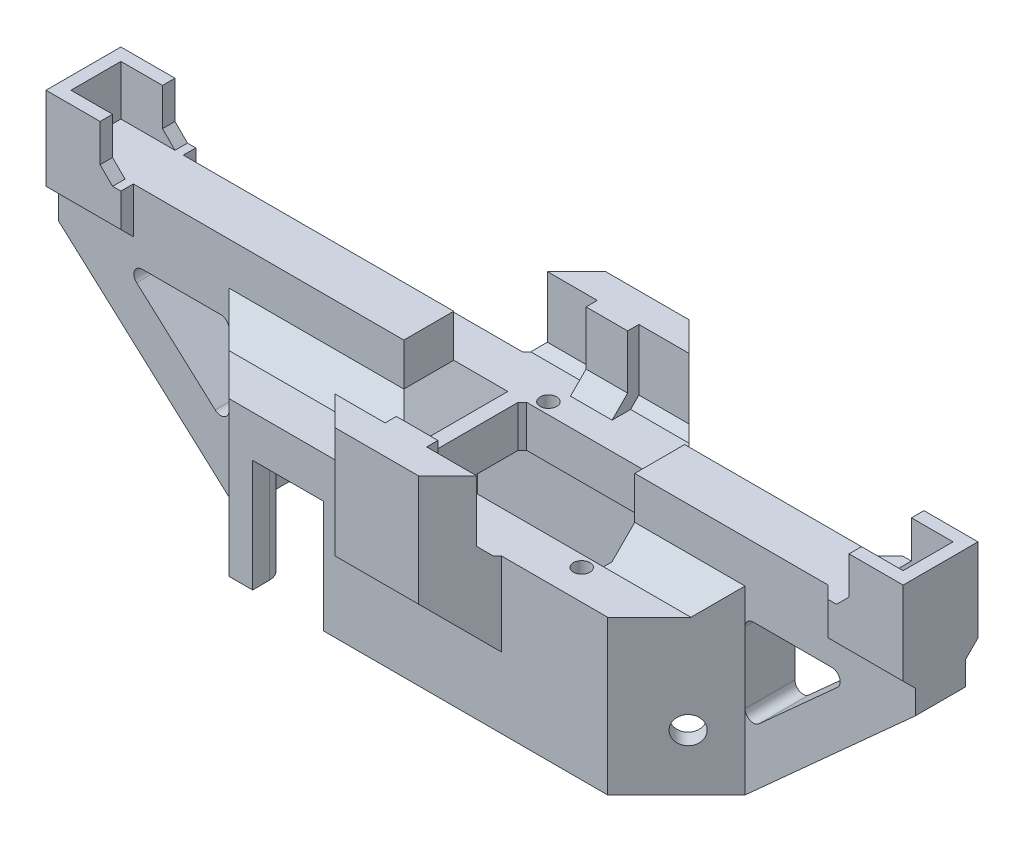
SolidWorks part; units mm, degrees
note: The reader was unsure of these and kept them because the rebuilt part matched: shared geometry of "Sketch17<3>".
ref_plane "Front Plane" through (0, 0, 0) normal (0, 0, 1) x (1, 0, 0)
ref_plane "Top Plane" through (0, 0, 0) normal (0, 1, 0) x (1, 0, 0)
ref_plane "Right Plane" through (0, 0, 0) normal (1, 0, 0) x (0, 0, -1)
sketch "Sketch1" plane through (0, 0, 0) normal (0, 1, 0) x (1, 0, 0)
  line L7 (-100, -6) -> (100, -6)
  line L8 (-100, -6) -> (-100, 6)
  line L9 (-100, 6) -> (100, 6)
  line L10 (100, -6) -> (100, 6)
  line L11 (-100, -6) -> (100, 6) construction
  line L12 (-100, 6) -> (100, -6) construction
  point P0 (0, 0)
  point P7 (0, 0)
  dimension "D2" = 200
  dimension "D3" = 12
extrude "Boss-Extrude2" add sketch "Sketch1" along normal blind 10
sketch "Sketch4" plane through (0, 0, 0) normal (0, 1, 0) x (1, 0, 0)
  line L1 (-10, -32.5) -> (10, -32.5)
  line L2 (-10, -32.5) -> (-10, 32.5)
  line L3 (-10, 32.5) -> (10, 32.5)
  line L4 (10, -32.5) -> (10, 32.5)
  line L5 (-10, -32.5) -> (10, 32.5) construction
  line L6 (-10, 32.5) -> (10, -32.5) construction
  point P0 (0, 0)
  dimension "D1" = 65
  dimension "D2" = 20
extrude "Boss-Extrude3" add sketch "Sketch4" along normal up to surface (10 mm away) up to face at (0, 10, 0)
sketch "Sketch5" plane through (0, 0, 0) normal (0, 1, 0) x (1, 0, 0)
  line L1 (-45.5, -22.5) -> (45.5, -22.5)
  line L2 (-45.5, -22.5) -> (-45.5, 22.5)
  line L3 (-45.5, 22.5) -> (45.5, 22.5)
  line L4 (45.5, -22.5) -> (45.5, 22.5)
  line L5 (-45.5, -22.5) -> (45.5, 22.5) construction
  line L6 (-45.5, 22.5) -> (45.5, -22.5) construction
  point P0 (0, 0)
  dimension "D1" = 91
  dimension "D2" = 45
extrude "Boss-Extrude4" add sketch "Sketch5" along normal up to surface (10 mm away) up to face at (0, 10, 0)
sketch "Sketch6" plane through (0, 10, 0) normal (0, 1, 0) x (1, 0, 0)
  line L1 (-10, -12.5) -> (35.5, -12.5)
  line L2 (-10, -12.5) -> (-10, 12.5)
  line L3 (-10, 12.5) -> (35.5, 12.5)
  line L4 (35.5, -12.5) -> (35.5, 12.5)
  line L5 (-10, -12.5) -> (35.5, 12.5) construction
  line L6 (-10, 12.5) -> (35.5, -12.5) construction
  point P0 (12.75, 0)
  dimension "D1" = 25
  dimension "D2" = 45.5
  dimension "D3" = 10
extrude "Cut-Extrude2" cut sketch "Sketch6" against normal through all
sketch "Sketch7" plane through (0, 10, 0) normal (0, 1, 0) x (1, 0, 0)
  line L0 (35.5, -12.5) -> (35.5, 12.5) construction
  line L1 (-100, 6) -> (-20, 6)
  line L2 (-100, 6) -> (-100, -6)
  line L3 (-100, -6) -> (-20, -6)
  line L4 (-20, 6) -> (-20, -6)
  line L5 (100, 6) -> (35.5, 6)
  line L6 (100, 6) -> (100, -6)
  line L7 (100, -6) -> (35.5, -6)
  line L8 (35.5, 6) -> (35.5, -6)
  line L9 (45.5, -6) -> (100, -6) construction
  line L10 (-100, -6) -> (-45.5, -6) construction
  dimension "D1" = 20
extrude "Boss-Extrude5" add sketch "Sketch7" along normal blind 16.7
sketch "Sketch8" plane through (0, 10, 0) normal (0, 1, 0) x (1, 0, 0)
  line L0 (10, 22.5) -> (10, 32.5) construction
  line L1 (-10, 32.5) -> (10, 32.5)
  line L2 (-10, 32.5) -> (-10, 25.5)
  line L3 (-10, 25.5) -> (10, 25.5)
  line L4 (10, 32.5) -> (10, 25.5)
  line L6 (-5, 22.8) -> (5, 22.8)
  line L7 (-5, 22.8) -> (-5, 25.5)
  line L8 (-5, 25.5) -> (5, 25.5)
  line L9 (5, 22.8) -> (5, 25.5)
  line L10 (-5, 22.8) -> (5, 25.5) construction
  line L11 (-5, 25.5) -> (5, 22.8) construction
  point P7 (0, 24.15)
  line M6 (10, 22.5) -> (10, 32.5)
  line M7 (10, 32.5) -> (-10, 32.5)
  line M8 (-10, 32.5) -> (-10, 22.5)
  dimension "D1" = 22.8
  dimension "D2" = 7
  dimension "D3" = 10
extrude "Boss-Extrude6" add sketch "Sketch8" along normal up to surface (16.7 mm away) contours L3 M8 M6 M7 | L6 L9 L3 L7 up to face at (67.75, 26.7, 0)
mirror "Mirror1" about plane through (0, 0, 0) normal (0, 0, 1) of "Boss-Extrude6"
chamfer "Chamfer1" distance 10 angle 45 4 edges at (-10, 5, 22.5) (10, 5, 22.5) (-10, 5, -22.5) (10, 5, -22.5)
chamfer "Chamfer3" distance 2 angle 45 4 edges at (11, 10, 25.5) (-11, 10, 25.5) (11, 10, -25.5) (-11, 10, -25.5)
chamfer "Chamfer4" distance 16.5 angle 45 4 edges at (45.5, 5, -6) (-45.5, 5, -6) (-45.5, 5, 6) (45.5, 5, 6)
chamfer "Chamfer5" distance 6.5 angle 45 1 edges at (-20, 10, 0)
chamfer "Chamfer6" distance 6.5 angle 45 4 edges at (-37.75, 10, -6) (48.75, 10, -6) (48.75, 10, 6) (-37.75, 10, 6)
chamfer "Chamfer7" distance 3.75 angle 45 2 edges at (0, 10, 22.8) (0, 10, -22.8)
sketch "Sketch9" plane through (0, 0, 6) normal (0, 0, 1) x (1, 0, 0)
  line L0 (-100, 26.7) -> (-100, 0) construction
  line L1 (-100, 18.7) -> (-85, 18.7)
  line L2 (-100, 18.7) -> (-100, 26.7)
  line L3 (-100, 26.7) -> (-85, 26.7)
  line L4 (-85, 18.7) -> (-85, 26.7)
  line L5 (-100, 26.7) -> (-20, 26.7) construction
  line L7 (-90, 26.7) -> (-100, 26.7)
  line L8 (-90, 26.7) -> (-90, 38.7)
  line L9 (-90, 38.7) -> (-100, 38.7)
  line L10 (-100, 26.7) -> (-100, 38.7)
  line M5 (-100, 26.7) -> (-100, 0)
  line M11 (-20, 26.7) -> (-100, 26.7)
  dimension "D1" = 10
  dimension "D2" = 8
  dimension "D3" = 12
  dimension "D4" = 15
extrude "Boss-Extrude7" add sketch "Sketch9" along normal blind 3 contours L10 L3 L8 L9 | L1 L4 L3 M11 M5
mirror "Mirror3" about plane through (0, 0, 0) normal (1, 0, 0) of "Boss-Extrude7" second plane through (0, 0, 0) second plane normal (0, 0, 1)
sketch "Sketch10" plane through (-100, 0, 0) normal (-1, 0, 0) x (0, 0, 1)
  line L0 (-6, 38.7) -> (6, 38.7)
  line L12 (6, 26.7) -> (-6, 26.7)
  line L13 (-6, 26.7) -> (-6, 38.7)
  line L14 (-6, 38.7) -> (-9, 38.7)
  line L15 (-9, 38.7) -> (-9, 18.7)
  line L16 (-9, 18.7) -> (-6, 18.7)
  line L17 (-6, 18.7) -> (-6, 0)
  line L18 (-6, 0) -> (6, 0)
  line L19 (6, 0) -> (6, 18.7)
  line L20 (6, 18.7) -> (9, 18.7)
  line L21 (9, 18.7) -> (9, 38.7)
  line L22 (9, 38.7) -> (6, 38.7)
  line L23 (6, 38.7) -> (6, 26.7)
  line L26 (-6, 38.7) -> (-9, 38.7)
  line L27 (-9, 38.7) -> (-9, 18.7)
  line L28 (-9, 18.7) -> (-6, 18.7)
  line L29 (-6, 18.7) -> (-6, 0)
  line L31 (6, 0) -> (6, 18.7)
  line L32 (6, 18.7) -> (9, 18.7)
  line L33 (9, 18.7) -> (9, 38.7)
  line L34 (9, 38.7) -> (6, 38.7)
  line L41 (-6, 0) -> (6, 0)
  dimension "D1" = 0
extrude "Boss-Extrude8" add sketch "Sketch10" along normal blind 3
mirror "Mirror4" about plane through (0, 0, 0) normal (1, 0, 0) of "Boss-Extrude8"
chamfer "Chamfer10" distance 3 angle 45 4 edges at (-90, 26.7, 7.5) (-90, 26.7, -7.5) (90, 26.7, 7.5) (90, 26.7, -7.5)
chamfer "Chamfer11" distance 3 angle 45 16 edges at (-94, 18.7, 6) (-85, 18.7, 7.5) (-94, 18.7, -6) (-85, 18.7, -7.5) (85, 26.7, 7.5) (85, 18.7, 7.5) (94, 18.7, 6) (85, 22.7, 6) (94, 18.7, -6) (85, 22.7, -6) (85, 18.7, -7.5) (85, 26.7, -7.5) (-103, 18.7, -7.5) (-103, 18.7, 7.5) (103, 18.7, 7.5) (103, 18.7, -7.5)
chamfer "Chamfer12" distance 1 angle 45 4 edges at (-10, 5, 12.5) (35.5, 5, 12.5) (35.5, 5, -12.5) (-10, 5, -12.5)
sketch "Sketch11" plane through (0, 0, 0) normal (0, -1, 0) x (1, 0, 0)
  line L0 (-20, 22.5) -> (20, 22.5)
  line L1 (-20, -22.5) -> (20, -22.5)
  line L2 (62, 6) -> (62, -6)
  line L3 (-62, 6) -> (-62, -6)
  line L4 (-58, 4.3431) -> (-58, -4.3431)
  line L5 (-58, -4.3431) -> (-43.8431, -18.5)
  line L6 (-43.8431, -18.5) -> (-20, -18.5)
  line L7 (-20, -18.5) -> (20, -18.5)
  line L8 (20, -18.5) -> (43.8431, -18.5)
  line L9 (43.8431, -18.5) -> (58, -4.3431)
  line L10 (58, 4.3431) -> (58, -4.3431)
  line L11 (58, 4.3431) -> (43.8431, 18.5)
  line L12 (43.8431, 18.5) -> (20, 18.5)
  line L13 (-20, 18.5) -> (20, 18.5)
  line L14 (-20, 18.5) -> (-43.8431, 18.5)
  line L15 (-43.8431, 18.5) -> (-58, 4.3431)
  line L20 (62, -6) -> (103, -6)
  line L21 (103, -6) -> (103, 6)
  line L22 (103, 6) -> (62, 6)
  line L23 (62, 6) -> (45.5, 22.5)
  line L24 (45.5, 22.5) -> (20, 22.5)
  line L25 (20, 22.5) -> (10, 32.5)
  line L26 (10, 32.5) -> (-10, 32.5)
  line L27 (-10, 32.5) -> (-20, 22.5)
  line L28 (-20, 22.5) -> (-45.5, 22.5)
  line L29 (-45.5, 22.5) -> (-62, 6)
  line L30 (-62, 6) -> (-103, 6)
  line L32 (-103, -6) -> (-62, -6)
  line L33 (-62, -6) -> (-45.5, -22.5)
  line L34 (-45.5, -22.5) -> (-20, -22.5)
  line L35 (-20, -22.5) -> (-10, -32.5)
  line L36 (-10, -32.5) -> (10, -32.5)
  line L37 (10, -32.5) -> (20, -22.5)
  line L38 (20, -22.5) -> (45.5, -22.5)
  line L39 (45.5, -22.5) -> (62, -6)
  line L43 (62, 6) -> (45.5, 22.5)
  line L44 (45.5, 22.5) -> (20, 22.5)
  line L48 (-20, 22.5) -> (-45.5, 22.5)
  line L49 (-45.5, 22.5) -> (-62, 6)
  line L53 (-62, -6) -> (-45.5, -22.5)
  line L54 (-45.5, -22.5) -> (-20, -22.5)
  line L58 (20, -22.5) -> (45.5, -22.5)
  line L59 (45.5, -22.5) -> (62, -6)
  line L76 (-103, 6) -> (-103, -6)
  dimension "D1" = 0
  dimension "D2" = 4
extrude "Boss-Extrude9" add sketch "Sketch11" along normal blind 27
chamfer "Chamfer13" distance 10 angle 45 2 edges at (0, 0, -22.5) (0, 0, 22.5)
sketch "Sketch14" plane through (0, 0, 0) normal (0, -1, 0) x (1, 0, 0)
  line L4 (62, 6) -> (62, -6)
  line L5 (62, -6) -> (103, -6)
  line L6 (103, -6) -> (103, 6)
  line L7 (103, 6) -> (62, 6)
  line L8 (62, 6) -> (62, -6)
  line L9 (62, -6) -> (103, -6)
  line L10 (103, -6) -> (103, 6)
  line L11 (103, 6) -> (62, 6)
  dimension "D1" = 0
extrude "Cut-Extrude4" cut sketch "Sketch14" against normal up to surface (10 mm away) up to face at (0.125, 10, 0)
sketch "Sketch16" plane through (0, 0, -6) normal (0, 0, -1) x (-1, 0, 0)
  line L0 (-103, 10) -> (-62, -27)
  line L1 (-62, -27) -> (-62, -13.53)
  line L2 (-62, -27) -> (-62, 10) construction
  line L3 (-62, -13.53) -> (-88.0738, 10)
  line L4 (-103, 10) -> (-62, 10) construction
  line L5 (-88.0738, 10) -> (-103, 10)
  dimension "D1" = 10
extrude "Boss-Extrude11" add sketch "Sketch16" against normal up to surface (12 mm away) up to face at (70.625, 17.225, 6)
mirror "Mirror6" about plane through (0, 0, 0) normal (1, 0, 0) of "Cut-Extrude4", "Boss-Extrude11"
fillet "Fillet2" radius 2 6 edges at (-62, -13.53, 0) (-62, 10, 0) (-88.0738, 10, 0) (62, -13.53, 0) (88.0738, 10, 0) (62, 10, 0)
sketch "Sketch17" plane through (0, 0, 0) normal (0, -1, 0) x (1, 0, 0)
  circle A0 centre (-43.8431, 18.5) radius 2
  circle A1 centre (-43.8431, 18.5) radius 4
  line M9 (43.8431, 18.5) -> (-43.8431, 18.5)
  line M10 (-43.8431, 18.5) -> (-58, 4.3431)
  dimension "D1" = 8
  dimension "D2" = 4
extrude "Boss-Extrude12" add sketch "Sketch17" along normal through all contours A1 A0 M10 M9
extrude "Cut-Extrude5" cut sketch "Sketch17<3>" along normal through all contours A0
sketch "Sketch17<3>" plane through (0, 0, 0) normal (0, -1, 0) x (1, 0, 0) same geometry as "Sketch17"
sketch "Sketch18" plane through (0, 0, 0) normal (0, -1, 0) x (1, 0, 0)
  circle A1 centre (-43.8431, 18.5) radius 2
  circle A2 centre (-43.8431, 18.5) radius 2
  dimension "D1" = 0
extrude "Boss-Extrude13" add sketch "Sketch18" along normal offset from surface (21 mm away) 6 up to face at (-4.6363, -27, 1.4878)
mirror "Mirror7" about plane through (0, 0, 0) normal (1, 0, 0) of "Cut-Extrude5", "Boss-Extrude13", "Boss-Extrude12" second plane through (0, 0, 0) second plane normal (0, 0, 1)
sketch "Sketch20" plane through (0, 10, 0) normal (0, 1, 0) x (1, 0, 0)
  line L0 (34.5, 12.5) -> (-9, 12.5) construction
  line L1 (-6.5, -15.25) -> (32, -15.25) construction
  line L2 (-6.5, -15.25) -> (-6.5, 15.25) construction
  line L3 (-6.5, 15.25) -> (32, 15.25) construction
  line L4 (32, -15.25) -> (32, 15.25) construction
  line L5 (-6.5, -15.25) -> (32, 15.25) construction
  line L6 (-6.5, 15.25) -> (32, -15.25) construction
  circle A0 centre (-6.5, 15.25) radius 1
  circle A1 centre (32, 15.25) radius 1
  circle A2 centre (32, -15.25) radius 1
  circle A3 centre (-6.5, -15.25) radius 1
  point P0 (12.75, 0)
  point P7 (12.75, 12.5)
  dimension "D3" = 2
  dimension "D1" = 38.5
  dimension "D2" = 30.5
extrude "Cut-Extrude7" cut sketch "Sketch20" against normal up to next
sketch "Sketch22" plane through (0, 10, 0) normal (0, 1, 0) x (1, 0, 0)
  circle A0 centre (-6.5, 15.25) radius 2
  circle A1 centre (32, 15.25) radius 2
  circle A2 centre (32, -15.25) radius 2
  circle A3 centre (-6.5, -15.25) radius 2
  dimension "D1" = 4
extrude "Cut-Extrude8" cut sketch "Sketch22" against normal offset from surface (6 mm away) 4 up to face at (-6.5, 0, -16.25)
sketch "Sketch23" plane through (0, 0, 0) normal (0, -1, 0) x (1, 0, 0)
  line L1 (-39.8431, -18.25) -> (-26.8431, -18.25)
  line L2 (-39.8431, -18.25) -> (-39.8431, 18.25)
  line L3 (-39.8431, 18.25) -> (-26.8431, 18.25)
  line L4 (-26.8431, -18.25) -> (-26.8431, 18.25)
  line L5 (-39.8431, -18.25) -> (-26.8431, 18.25) construction
  line L6 (-39.8431, 18.25) -> (-26.8431, -18.25) construction
  point P0 (-33.3431, 0)
  dimension "D1" = 13
  dimension "D2" = 36.5
extrude "Cut-Extrude9" cut sketch "Sketch23" against normal blind 5
sketch "Sketch24" plane through (0, 0, 0) normal (0, -1, 0) x (1, 0, 0)
  line L0 (45.5, 22.5) -> (-45.5, 22.5) construction
  line L1 (-39.8431, 22.5) -> (-26.8431, 22.5)
  line L2 (-39.8431, 22.5) -> (-39.8431, -22.5)
  line L3 (-39.8431, -22.5) -> (-26.8431, -22.5)
  line L4 (-26.8431, 22.5) -> (-26.8431, -22.5)
  line L5 (-45.5, -22.5) -> (45.5, -22.5) construction
  line L6 (-26.8431, -18.25) -> (-26.8431, 18.25) construction
  line L7 (-39.8431, 18.25) -> (-39.8431, -18.25) construction
extrude "Cut-Extrude10" cut sketch "Sketch24" along normal through all
chamfer "Chamfer14" distance 4 angle 45 2 edges at (-26.8431, -13.5, -22.5) (-26.8431, -13.5, 22.5)
fillet "Fillet4" radius 1 2 edges at (-33.3431, 5, 18.25) (-33.3431, 5, -18.25)
sketch "Sketch25" plane through (-31.1716, 0, -31.1716) normal (0.7071, 0, 0.7071) x (0.7071, 0, -0.7071)
  line L0 (-37.9411, -27) -> (-21.9203, -27) construction
  line L1 (-33.9411, -19) -> (-25.9203, -19)
  line L2 (-33.9411, -19) -> (-33.9411, 0)
  line L3 (-33.9411, 0) -> (-25.9203, 0)
  line L4 (-25.9203, -19) -> (-25.9203, 0)
  line L5 (-33.9411, -19) -> (-25.9203, 0) construction
  line L6 (-33.9411, 0) -> (-25.9203, -19) construction
  line L7 (-37.9411, -27) -> (-37.9411, 0) construction
  line L8 (-21.9203, -27) -> (-21.9203, 0) construction
  line L9 (-37.9411, 0) -> (-21.9203, 0) construction
  point P0 (-29.9307, -9.5)
  dimension "D1" = 8
  dimension "D2" = 4
  dimension "D3" = 4
extrude "Cut-Extrude11" cut sketch "Sketch25" against normal up to next
mirror "Mirror12" about plane through (0, 0, 0) normal (0, 0, 1) of "Cut-Extrude11"
mirror "Mirror13" about plane through (0, 0, 0) normal (1, 0, 0) of "Cut-Extrude11"
sketch "Sketch26" plane through (31.1716, 0, 31.1716) normal (-0.7071, 0, -0.7071) x (-0.7071, 0, 0.7071)
  line L0 (-37.9411, 0) -> (-21.9203, 0) construction
  line L1 (-37.9411, -27) -> (-37.9411, 0) construction
  circle A0 centre (-29.9307, -13.5) radius 3.25
  point P2 (-29.9307, 0)
  point P3 (-37.9411, -13.5)
  dimension "D1" = 6.5
extrude "Cut-Extrude12" cut sketch "Sketch26" against normal up to next
fillet "Fillet5" radius 2 12 edges at (-50.9142, -19, 14.2574) (-56.5858, -19, 8.5858) (-56.5858, 0, 8.5858) (-50.9142, 0, 14.2574) (-50.9142, -19, -14.2574) (-56.5858, -19, -8.5858) (-56.5858, 0, -8.5858) (-50.9142, 0, -14.2574) (56.5858, -19, -8.5858) (50.9142, -19, -14.2574) (50.9142, 0, -14.2574) (56.5858, 0, -8.5858)
